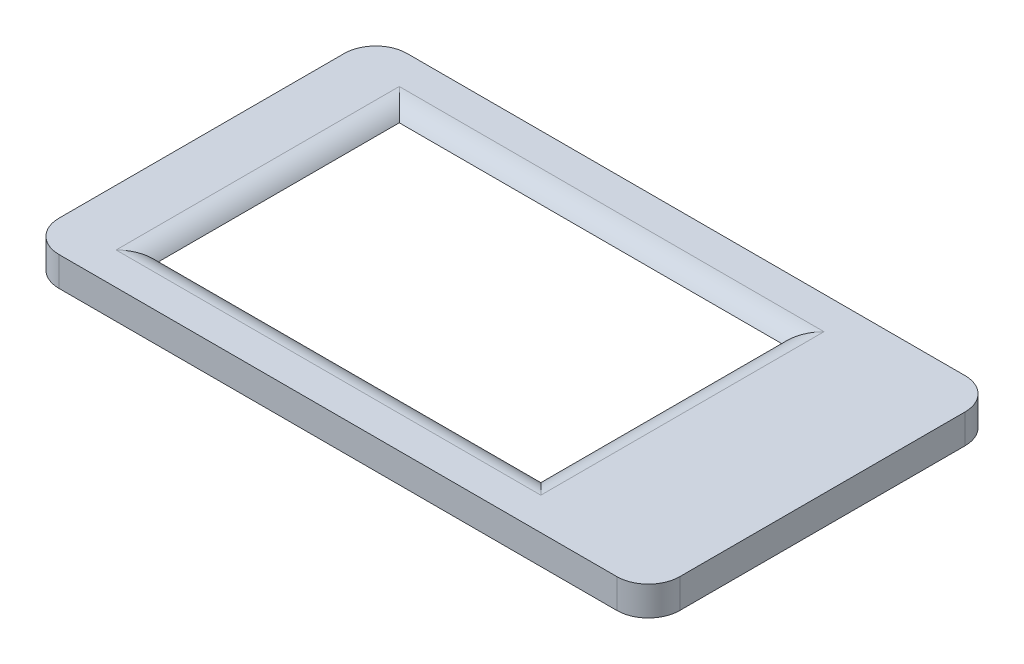
SolidWorks part; units mm, degrees
material "ABS"
ref_plane "Спереди" through (0, 0, 0) normal (0, 0, 1) x (1, 0, 0)
ref_plane "Сверху" through (0, 0, 0) normal (0, 1, 0) x (1, 0, 0)
ref_plane "Справа" through (0, 0, 0) normal (1, 0, 0) x (0, 0, -1)
sketch "Эскиз1" plane through (0, 0, 0) normal (0, 1, 0) x (1, 0, 0)
  line L0 (-61.2, 33.2) -> (57.2, 33.2)
  line L1 (57.2, 33.2) -> (57.2, -33.2)
  line L2 (-61.2, -33.2) -> (57.2, -33.2)
  line L4 (-61.2, 33.2) -> (-61.2, -33.2)
  point P0 (0, 0)
extrude "Бобышка-Вытянуть1" add sketch "Эскиз1" along normal blind 5.6
sketch "Эскиз5" plane through (0, 0, 0) normal (0, -1, 0) x (1, 0, 0)
  circle A0 centre (-56.16, 21.1) radius 3
  circle A1 centre (-56.16, -21.9) radius 3
  circle A2 centre (35.96, 22.3) radius 3
  circle A3 centre (35.96, -18.7) radius 3
extrude "под гайку" cut sketch "Эскиз5" against normal blind 3
sketch "Эскиз7" plane through (0, 0, 0) normal (0, -1, 0) x (1, 0, 0)
  line L0 (32.5, 29) -> (-52.5, 29)
  line L1 (32.5, -29) -> (-52.5, -29)
  line L7 (32.5, -29) -> (32.5, 29)
  line L9 (-52.5, -29) -> (-52.5, 29)
extrude "под LCD" cut sketch "Эскиз7" against normal blind 3.6
sketch "Эскиз11" [suppressed] plane through (0, 5.6, 0) normal (0, 1, 0) x (1, 0, 0)
  line L0 (-12.6056, 22.5401) -> (-12.6056, -41.5105) construction
sketch "Эскиз13" plane through (0, 3.6, 0) normal (0, -1, 0) x (1, 0, 0)
  line L1 (-46.5, 23) -> (26.5, 23)
  line L2 (-46.5, 23) -> (-46.5, -23)
  line L3 (-46.5, -23) -> (26.5, -23)
  line L4 (26.5, 23) -> (26.5, -23)
extrude "Вырез-Вытянуть1" cut sketch "Эскиз13" against normal blind 10
fillet "Скругление2" radius 5 4 edges at (-46.5, 5.6, 0) (-10, 5.6, 23) (-10, 5.6, -23) (26.5, 5.6, 0)
fillet "Скругление3" radius 6 4 edges at (-61.2, 2.8, 33.2) (-61.2, 2.8, -33.2) (57.2, 2.8, 33.2) (57.2, 2.8, -33.2)
